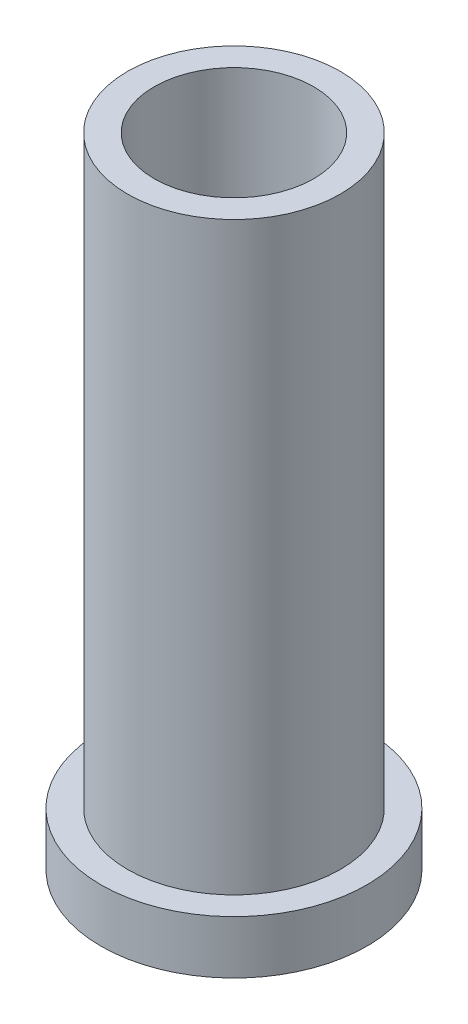
SolidWorks part; units mm, degrees
ref_plane "Front Plane" through (0, 0, 0) normal (0, 0, 1) x (1, 0, 0)
ref_plane "Top Plane" through (0, 0, 0) normal (0, 1, 0) x (1, 0, 0)
ref_plane "Right Plane" through (0, 0, 0) normal (1, 0, 0) x (0, 0, -1)
sketch "Sketch2" plane through (0, 0, 0) normal (0, 1, 0) x (1, 0, 0)
  circle A0 centre (0, 0) radius 38.1
  circle A1 centre (0, 0) radius 50.8
  dimension "D1" = 101.6
  dimension "D2" = 76.2
extrude "Boss-Extrude1" add sketch "Sketch2" along normal blind 304.8
sketch "Sketch4" plane through (0, 0, 0) normal (0, 1, 0) x (1, 0, 0)
  circle A0 centre (0, 0) radius 63.5
  circle A1 centre (0, 0) radius 38.1
  dimension "D1" = 127
extrude "Boss-Extrude3" add sketch "Sketch4" along normal blind 25.4
